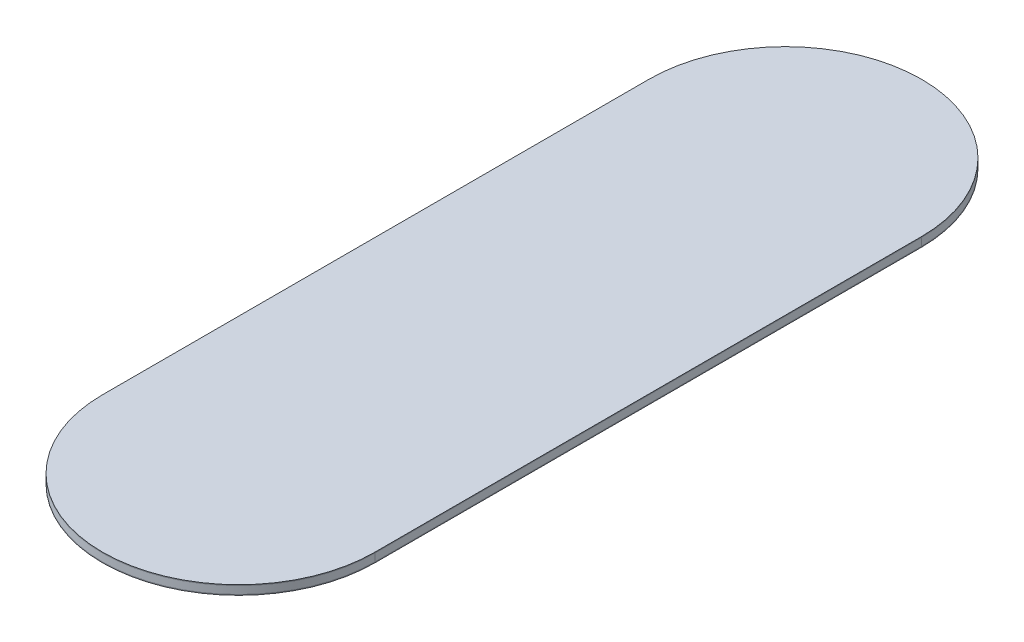
SolidWorks part; units mm, degrees
ref_plane "Front Plane" through (0, 0, 0) normal (0, 0, 1) x (1, 0, 0)
ref_plane "Top Plane" through (0, 0, 0) normal (0, 1, 0) x (1, 0, 0)
ref_plane "Right Plane" through (0, 0, 0) normal (1, 0, 0) x (0, 0, -1)
sketch "Sketch1" plane through (0, 0, 0) normal (0, 1, 0) x (1, 0, 0)
  line L0 (0, -88.9) -> (0, 88.9) construction
  line L2 (44.323, 88.9) -> (44.323, -88.9)
  line L3 (0, 0) -> (-26.323, 0) construction
  line L14 (-44.323, 88.9) -> (-44.323, -88.9)
  arc A0 (44.323, 88.9) -> (-44.323, 88.9) centre (0, 88.9) ccw
  arc A1 (-44.323, -88.9) -> (44.323, -88.9) centre (0, -88.9) ccw
  point P8 (0, 0)
  point P13 (-89.4761, 0)
  point P18 (-35.323, 0)
  dimension "D2" = 88.646
  dimension "D1" = 177.8
extrude "Boss-Extrude1" add sketch "Sketch1" along normal blind 0.25
sketch "Sketch5" plane through (0, 0.25, 0) normal (0, 1, 0) x (1, 0, 0)
  line L2 (-44.323, 88.9) -> (-44.323, -88.9)
  line L3 (44.323, -88.9) -> (44.323, 88.9)
  line L4 (-44.323, 88.9) -> (-44.323, -88.9)
  line L5 (44.323, -88.9) -> (44.323, 88.9)
  arc A2 (44.323, 88.9) -> (-44.323, 88.9) centre (0, 88.9) ccw
  arc A3 (-44.323, -88.9) -> (44.323, -88.9) centre (0, -88.9) ccw
  arc A4 (44.323, 88.9) -> (-44.323, 88.9) centre (0, 88.9) ccw
  arc A5 (-44.323, -88.9) -> (44.323, -88.9) centre (0, -88.9) ccw
  dimension "D1" = 0
extrude "Boss-Extrude6" add sketch "Sketch5" along normal blind 2.5 separate body
sketch "Sketch6" plane through (0, 2.75, 0) normal (0, 1, 0) x (1, 0, 0)
  line L2 (-44.323, 88.9) -> (-44.323, -88.9)
  line L3 (44.323, -88.9) -> (44.323, 88.9)
  line L4 (-44.323, 88.9) -> (-44.323, -88.9)
  line L5 (44.323, -88.9) -> (44.323, 88.9)
  arc A2 (44.323, 88.9) -> (-44.323, 88.9) centre (0, 88.9) ccw
  arc A3 (-44.323, -88.9) -> (44.323, -88.9) centre (0, -88.9) ccw
  arc A4 (44.323, 88.9) -> (-44.323, 88.9) centre (0, 88.9) ccw
  arc A5 (-44.323, -88.9) -> (44.323, -88.9) centre (0, -88.9) ccw
  dimension "D1" = 0
extrude "Boss-Extrude7" add sketch "Sketch6" along normal blind 0.25 separate body
